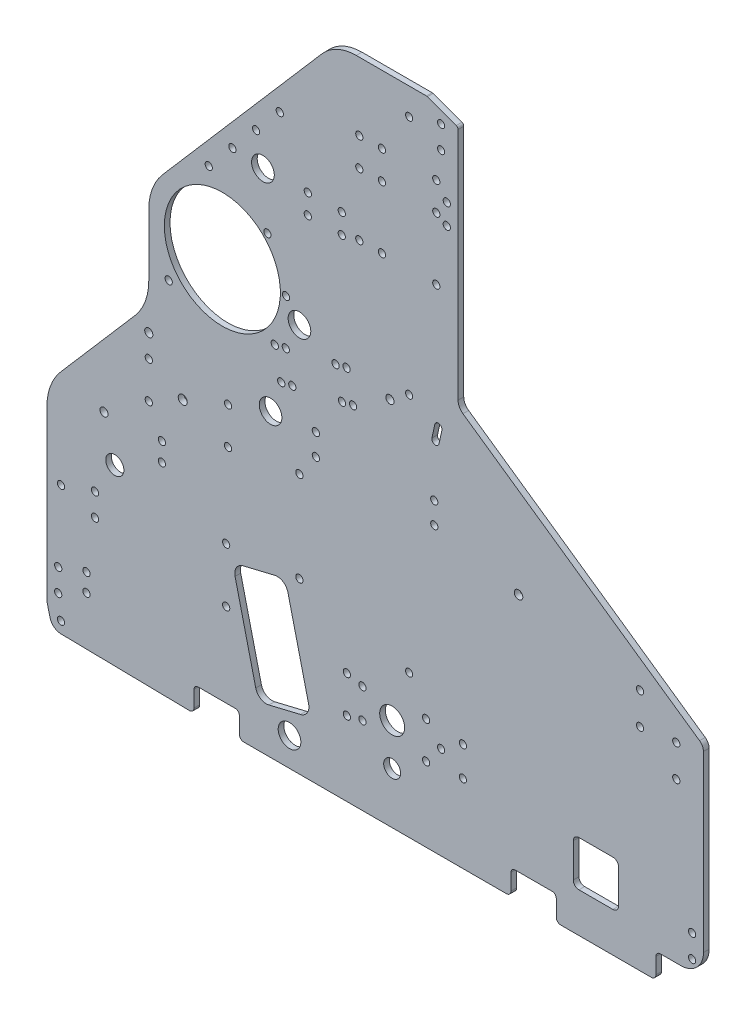
SolidWorks part; units mm, degrees
ref_plane "Front Plane" through (0, 0, 0) normal (0, 0, 1) x (1, 0, 0)
ref_plane "Top Plane" through (0, 0, 0) normal (0, 1, 0) x (1, 0, 0)
ref_plane "Right Plane" through (0, 0, 0) normal (1, 0, 0) x (0, 0, -1)
sketch "Sketch1" plane through (0, 0, 0) normal (0, 0, 1) x (1, 0, 0)
  line L0 (82.55, -20.32) -> (82.55, -6.35)
  line L2 (0, 0) -> (0, 157.48)
  line L4 (368.3, -20.32) -> (368.3, 106.68)
  line L5 (82.55, -6.35) -> (107.95, -6.35)
  line L6 (107.95, -6.35) -> (107.95, -20.32)
  line L7 (107.95, -20.32) -> (260.35, -20.32)
  line L8 (260.35, -20.32) -> (260.35, -6.35)
  line L9 (260.35, -6.35) -> (285.75, -6.35)
  line L10 (285.75, -6.35) -> (285.75, -20.32)
  line L11 (285.75, -20.32) -> (368.3, -20.32)
  line L12 (361.95, 12.7) -> (368.3, 12.7) construction
  line L13 (0, 0) -> (6.35, 0) construction
  line L14 (0.1896, -7.8901) -> (1.7771, -14.2401)
  line L15 (7.8295, -19.0491) -> (82.55, -20.32)
  line L16 (0, 0) -> (0, -6.35)
  line L17 (76.2, 128.905) -> (79.375, 128.905) construction
  line L18 (57.15, 118.5863) -> (101.6, 118.5862) construction
  line L19 (57.15, 118.5863) -> (57.15, 139.2238) construction
  line L20 (101.6, 118.5862) -> (101.6, 139.2237) construction
  line L21 (57.15, 139.2238) -> (101.6, 139.2237) construction
  line L22 (57.15, 118.5863) -> (101.6, 139.2237) construction
  line L23 (101.6, 118.5862) -> (57.15, 139.2238) construction
  line L24 (101.6, 139.2237) -> (125.4682, 147.9111) construction
  line L25 (203.2, 59.805) -> (203.2, 194.805) construction
  line L26 (203.2, 194.805) -> (203.2, 329.805) construction
  line L27 (355.6, 332.105) -> (330.2, 332.105) construction
  line L28 (330.2, 332.105) -> (330.2, 217.805) construction
  line L29 (330.2, 217.805) -> (355.6, 217.805) construction
  line L30 (355.6, 217.805) -> (355.6, 332.105) construction
  line L31 (203.2, 344.805) -> (203.2, 194.805) construction
  line L32 (50.8, 332.105) -> (76.2, 332.105) construction
  line L33 (76.2, 332.105) -> (76.2, 217.805) construction
  line L34 (50.8, 217.805) -> (50.8, 332.105) construction
  line L35 (76.2, 217.805) -> (50.8, 217.805) construction
  line L36 (213.2, 344.805) -> (230.6638, 338.455)
  line L37 (203.2, 344.805) -> (161.925, 344.805)
  line L38 (203.2, 344.805) -> (213.2, 344.805)
  line L39 (348.5362, 344.805) -> (413.4623, 344.805)
  line L40 (348.5362, 344.805) -> (230.6638, 344.805) construction
  line L42 (161.925, 344.805) -> (0, 157.48)
  line L44 (230.6638, 338.455) -> (230.6638, 202.565)
  line L45 (230.6638, 202.565) -> (368.3, 106.68)
  line L46 (213.2, 344.805) -> (-141.0713, 344.805) construction
  circle A0 centre (6.35, 0) radius 2.032
  circle A1 centre (6.35, 12.7) radius 2.032
  circle A2 centre (361.95, 0) radius 2.032
  circle A3 centre (361.95, 12.7) radius 2.032
  arc A5 (1.7771, -14.2401) -> (7.8295, -19.0491) centre (7.9375, -12.7) ccw
  circle A6 centre (7.9375, -12.7) radius 2.032
  arc A7 (0, -6.35) -> (0.1896, -7.8901) centre (6.35, -6.35) ccw
  circle A8 centre (38.1, 78.105) radius 5.08
  circle A9 centre (76.2, 128.905) radius 2.54
  circle A10 centre (101.6, 118.5862) radius 2.032
  circle A11 centre (101.6, 139.2237) radius 2.032
  circle A12 centre (57.15, 139.2238) radius 2.032
  circle A13 centre (57.15, 118.5863) radius 2.032
  circle A15 centre (203.2, 59.805) radius 2
  circle A16 centre (203.2, 194.805) radius 2
  circle A17 centre (203.2, 329.805) radius 2
  circle A18 centre (63.5, 313.055) radius 2.032
  circle A20 centre (355.6, 332.105) radius 2.032
  circle A21 centre (330.2, 332.105) radius 2.032
  circle A22 centre (355.6, 217.805) radius 2.032
  circle A23 centre (330.2, 217.805) radius 2.032
  circle A24 centre (50.8, 332.105) radius 2.032
  circle A25 centre (76.2, 332.105) radius 2.032
  circle A26 centre (50.8, 217.805) radius 2.032
  circle A27 centre (76.2, 217.805) radius 2.032
  circle A28 centre (221.1381, 335.28) radius 2
  circle A29 centre (224.3138, 298.831) radius 2.032
  circle A30 centre (353.06, 100.7351) radius 2.032
  circle A31 centre (332.74, 115.9751) radius 2.032
  circle A32 centre (332.74, 98.1951) radius 2.032
  circle A33 centre (353.06, 82.9551) radius 2.032
  circle A34 centre (117.3562, 280.4276) radius 2.032
  circle A35 centre (104.0678, 265.0548) radius 2.032
  circle A36 centre (90.7795, 249.682) radius 2.032
  circle A38 centre (130.6445, 295.8004) radius 2.032
  circle A39 centre (68.326, 182.9237) radius 2.032
  circle A40 centre (224.3138, 287.401) radius 2.032
  circle A41 centre (125.4682, 147.9111) radius 6.35
  circle A42 centre (221.1381, 322.58) radius 2
  point P82 (203.2, 344.805)
  point P90 (368.3, 62.484)
  dimension "D6" = 4.064
  dimension "D10" = 6.35
  dimension "D11" = 4.064
  dimension "D17" = 38.1
  dimension "D27" = 4
  dimension "D31" = 4.064
  dimension "D32" = 41.275
  dimension "D36" = 4.064
  dimension "D47" = 39.624
  dimension "D48" = 4.064
  dimension "D25" = 5.08
  dimension "D26" = 4.064
  dimension "D52" = 4.064
  dimension "D65" = 4.064
  dimension "D69" = 10.16
  dimension "D72" = 12.7
  dimension "D2" = 127
  dimension "D3" = 13.97
  dimension "D4" = 25.4
  dimension "D5" = 152.4
  dimension "D7" = 12.7
  dimension "D8" = 6.35
  dimension "D9" = 20.32
  dimension "D12" = 12.7
  dimension "D13" = 1.5875
  dimension "D14" = 82.55
  dimension "D15" = 368.3
  dimension "D16" = 6.35
  dimension "D18" = 98.425
  dimension "D19" = 38.1
  dimension "D20" = 50.8
  dimension "D21" = 3.175
  dimension "D22" = 270
  dimension "D23" = 20.6375
  dimension "D24" = 44.45
  dimension "D28" = 135
  dimension "D29" = 12.7
  dimension "D30" = 15
  dimension "D33" = 63.5
  dimension "D34" = 27.4638
  dimension "D35" = 12.7
  dimension "D37" = 114.3
  dimension "D38" = 25.4
  dimension "D39" = 12.7
  dimension "D40" = 157.48
  dimension "D41" = 142.24
  dimension "D42" = 365.125
  dimension "D43" = 10
  dimension "D44" = 6.35
  dimension "D45" = 31.75
  dimension "D46" = 3.175
  dimension "D49" = 6.35
  dimension "D50" = 203.2
  dimension "D51" = 15.24
  dimension "D53" = 17.78
  dimension "D54" = 17.78
  dimension "D55" = 20.32
  dimension "D56" = 15.24
  dimension "D57" = 92.202
  dimension "D58" = 8.382
  dimension "D59" = 20.32
  dimension "D60" = 20.32
  dimension "D61" = 8.382
  dimension "D62" = 20.32
  dimension "D63" = 8.382
  dimension "D64" = 8.382
  dimension "D66" = 35.052
  dimension "D67" = 68.326
  dimension "D68" = 11.43
  dimension "D70" = 25.4
  dimension "D71" = 110
  dimension "D73" = 17.9381
  dimension "D74" = 12.7
extrude "Boss-Extrude1" add sketch "Sketch1" along normal blind 3.175 contours L16 A7 L14 A5 L15 L2 A0 A1 A6 region at (171.5045, 119.4976, 0)
fillet "Fillet1" radius 2.286 4 edges at (285.75, -6.35, 1.5875) (107.95, -6.35, 1.5875) (260.35, -6.35, 1.5875) (82.55, -6.35, 1.5875)
fillet "Fillet2" radius 6.35 1 edges at (230.6638, 202.565, 1.5875)
sketch "Sketch2" plane through (0, 0, 0) normal (0, 0, -1) x (-1, 0, 0)
  circle A0 centre (-100.5528, 71.086) radius 2.032 construction
  circle A1 centre (-100.5528, 40.606) radius 2.032 construction
  circle A2 centre (-22.225, 18.2025) radius 2.032 construction
  circle A3 centre (-22.225, 8.0425) radius 2.032 construction
  circle A4 centre (-100.5528, 71.086) radius 2.032
  circle A5 centre (-100.5528, 40.606) radius 2.032
  circle A6 centre (-22.225, 18.2025) radius 2.032
  circle A7 centre (-22.225, 8.0425) radius 2.032
extrude "Cut-Extrude1" cut sketch "Sketch2" against normal through all
fillet "Fillet3" radius 1.5875 2 edges at (230.6638, 338.455, 1.5875) (213.2, 344.805, 1.5875)
sketch "Sketch3" plane through (0, 0, 3.175) normal (0, 0, 1) x (1, 0, 0)
  line L0 (132.9524, 63.2646) -> (132.7215, 64.2281) construction
  line L1 (128.3814, 66.8897) -> (110.6828, 62.6472) construction
  line L2 (114.5132, 58.4237) -> (126.8822, 61.3887) construction
  line L3 (108.0212, 58.3071) -> (108.2522, 57.3436) construction
  line L4 (131.2006, 57.703) -> (140.0164, 20.9265) construction
  line L5 (144.0993, 16.7636) -> (132.9524, 63.2646) construction
  line L6 (108.2522, 57.3436) -> (119.3991, 10.8426) construction
  line L7 (121.1509, 16.4042) -> (112.3351, 53.1807) construction
  line L8 (119.3991, 10.8426) -> (119.6301, 9.8791) construction
  line L9 (144.3303, 15.8001) -> (144.0993, 16.7636) construction
  line L10 (137.8383, 15.6835) -> (125.4694, 12.7185) construction
  line L11 (123.9701, 7.2175) -> (141.6687, 11.4601) construction
  line L12 (132.9524, 63.2646) -> (132.7215, 64.2281)
  line L13 (128.3814, 66.8897) -> (110.6828, 62.6472)
  line L14 (114.5132, 58.4237) -> (126.8822, 61.3887)
  line L15 (108.0212, 58.3071) -> (108.2522, 57.3436)
  line L16 (131.2006, 57.703) -> (140.0164, 20.9265)
  line L17 (144.0993, 16.7636) -> (132.9524, 63.2646)
  line L18 (108.2522, 57.3436) -> (119.3991, 10.8426)
  line L19 (121.1509, 16.4042) -> (112.3351, 53.1807)
  line L20 (119.3991, 10.8426) -> (119.6301, 9.8791)
  line L21 (144.3303, 15.8001) -> (144.0993, 16.7636)
  line L22 (137.8383, 15.6835) -> (125.4694, 12.7185)
  line L23 (123.9701, 7.2175) -> (141.6687, 11.4601)
  line L24 (127.7894, 69.3598) -> (110.0908, 65.1172)
  line L25 (105.5512, 57.715) -> (105.7822, 56.7515)
  line L26 (105.7822, 56.7515) -> (116.9291, 10.2505)
  line L27 (116.9291, 10.2505) -> (117.16, 9.287)
  line L28 (124.5622, 4.7475) -> (142.2608, 8.99)
  line L29 (146.8003, 16.3922) -> (146.5694, 17.3557)
  line L30 (146.5694, 17.3557) -> (135.4225, 63.8567)
  line L31 (135.4225, 63.8567) -> (135.1915, 64.8202)
  line L32 (14.605, -0.1369) -> (103.7278, 32.3011) construction
  line L33 (14.605, -0.1369) -> (103.7278, 32.3011)
  line L34 (0, -6.35) -> (0, 157.48) construction
  line L35 (-39.6666, 74.7152) -> (103.7278, 126.9065) construction
  line L36 (26.9875, 46.9531) -> (26.9875, 59.6531) construction
  line L37 (107.95, -20.32) -> (260.35, -20.32) construction
  line L38 (64.5259, 92.5258) -> (64.5259, 102.9405) construction
  line L39 (131.6538, 14.201) -> (136.0946, -4.3242) construction
  arc A0 (132.7215, 64.2281) -> (128.6308, 66.9403) centre (129.2206, 63.3889) ccw construction
  arc A1 (110.6828, 62.6472) -> (110.4377, 62.5791) centre (111.522, 59.1463) ccw construction
  arc A2 (128.6308, 66.9403) -> (128.3814, 66.8897) centre (129.2206, 63.3889) ccw construction
  arc A3 (110.4377, 62.5791) -> (108.0212, 58.3071) centre (111.522, 59.1463) ccw construction
  arc A4 (119.6301, 9.8791) -> (123.7207, 7.1669) centre (123.1309, 10.7183) ccw construction
  arc A5 (141.9139, 11.5281) -> (144.3303, 15.8001) centre (140.8295, 14.9609) ccw construction
  arc A6 (141.6687, 11.4601) -> (141.9139, 11.5281) centre (140.8295, 14.9609) ccw construction
  arc A7 (123.7207, 7.1669) -> (123.9701, 7.2175) centre (123.1309, 10.7183) ccw construction
  arc A8 (132.7215, 64.2281) -> (128.6308, 66.9403) centre (129.2206, 63.3889) ccw
  arc A9 (110.6828, 62.6472) -> (110.4377, 62.5791) centre (111.522, 59.1463) ccw
  arc A10 (128.6308, 66.9403) -> (128.3814, 66.8897) centre (129.2206, 63.3889) ccw
  arc A11 (110.4377, 62.5791) -> (108.0212, 58.3071) centre (111.522, 59.1463) ccw
  arc A12 (119.6301, 9.8791) -> (123.7207, 7.1669) centre (123.1309, 10.7183) ccw
  arc A13 (141.9139, 11.5281) -> (144.3303, 15.8001) centre (140.8295, 14.9609) ccw
  arc A14 (141.6687, 11.4601) -> (141.9139, 11.5281) centre (140.8295, 14.9609) ccw
  arc A15 (123.7207, 7.1669) -> (123.9701, 7.2175) centre (123.1309, 10.7183) ccw
  arc A16 (110.0908, 65.1172) -> (109.6726, 65.0012) centre (111.522, 59.1463) ccw
  arc A17 (109.6726, 65.0012) -> (105.5512, 57.715) centre (111.522, 59.1463) ccw
  arc A18 (117.16, 9.287) -> (124.1369, 4.6613) centre (123.1309, 10.7183) ccw
  arc A19 (124.1369, 4.6613) -> (124.5622, 4.7475) centre (123.1309, 10.7183) ccw
  arc A20 (142.2608, 8.99) -> (142.6789, 9.1061) centre (140.8295, 14.9609) ccw
  arc A21 (142.6789, 9.1061) -> (146.8003, 16.3922) centre (140.8295, 14.9609) ccw
  arc A22 (135.1915, 64.8202) -> (128.2147, 69.446) centre (129.2206, 63.3889) ccw
  arc A23 (128.2147, 69.446) -> (127.7894, 69.3598) centre (129.2206, 63.3889) ccw
  circle A24 centre (136.0946, -4.3242) radius 6.35
  circle A26 centre (134.1437, 208.2281) radius 2.032 construction
  circle A33 centre (26.9875, 46.9531) radius 2.032
  circle A34 centre (26.9875, 59.6531) radius 2.032
  circle A35 centre (7.9375, 53.3031) radius 2.032
  circle A37 centre (32.0306, 100.8109) radius 32.385 construction
  circle A38 centre (32.0306, 100.8109) radius 2.286
  circle A39 centre (123.682, 233.4851) radius 2.032 construction
  circle A40 centre (64.5259, 102.9405) radius 2.032
  circle A41 centre (64.5259, 92.5258) radius 2.032
  circle A42 centre (134.1437, 208.2281) radius 2.032
  circle A43 centre (123.682, 233.4851) radius 2.032
  ellipse E0 centre (124.5974, 48.8487) end of major axis (128.5376, 61.3578) minor radius 6 (131.2006, 57.703) -> (126.8822, 61.3887) ccw construction
  ellipse E1 centre (122.2349, 48.2824) end of major axis (113.0518, 57.6456) minor radius 6 (114.5132, 58.4237) -> (112.3351, 53.1807) ccw construction
  ellipse E2 centre (127.7541, 25.2585) end of major axis (131.6942, 37.7675) minor radius 6 (121.1509, 16.4042) -> (125.4694, 12.7185) ccw construction
  ellipse E3 centre (130.1166, 25.8248) end of major axis (139.2998, 16.4616) minor radius 6 (137.8383, 15.6835) -> (140.0164, 20.9265) ccw construction
  ellipse E4 centre (124.5974, 48.8487) end of major axis (120.6573, 36.3397) minor radius 6 (131.2006, 57.703) -> (126.8822, 61.3887) ccw
  ellipse E5 centre (122.2349, 48.2824) end of major axis (131.4181, 38.9192) minor radius 6 (114.5132, 58.4237) -> (112.3351, 53.1807) ccw
  ellipse E6 centre (127.7541, 25.2585) end of major axis (131.6942, 37.7675) minor radius 6 (121.1509, 16.4042) -> (125.4694, 12.7185) ccw
  ellipse E7 centre (130.1166, 25.8248) end of major axis (139.2998, 16.4616) minor radius 6 (137.8383, 15.6835) -> (140.0164, 20.9265) ccw
  point P93 (26.9875, 53.3031)
  point P115 (32.0306, 100.8109)
  dimension "D3" = 64.77
  dimension "D4" = 4.572
  dimension "D8" = 4.064
  dimension "D13" = 12.7
  dimension "D2" = 88.9
  dimension "D5" = 7.9375
  dimension "D6" = 19.05
  dimension "D7" = 73.6231
  dimension "D9" = 12.7
  dimension "D10" = 10.4147
  dimension "D11" = 37.5384
  dimension "D12" = 45.5727
  dimension "D14" = 19.05
  dimension "D1" = 2.54
extrude "Cut-Extrude2" cut sketch "Sketch3" against normal through all contours A22 A23 L24 A16 A17 L25 L26 L27 A18 A19 L28 A20 A21 L29 L30 L31 A15 A12 L20 L18 L15 A11 A9 L13 A10 A8 L12 L17 L21 A13 A14 L23 | A12 A15 L23 A14 A13 L21 L17 L12 A8 A10 L13 A9 A11 L15 L18 L20 E7 L22 E6 L19 E5 L14 E4 L16 | L22 E7 L16 E4 L14 E5 L19 E6 | A38 | A41 | A40 | A35 | A34 | A33 | A43 | A42 | A24 region at (137.844, 39.8506, 3.175) region at (126.1758, 37.0536, 3.175) region at (128.1544, 68.6507, 3.175) region at (32.0306, 100.8109, 3.175) region at (64.5259, 102.9405, 3.175) region at (64.5259, 92.5258, 3.175)
sketch "Sketch4" plane through (0, 0, 3.175) normal (0, 0, 1) x (1, 0, 0)
  line L0 (57.15, 139.2238) -> (101.6, 139.2237) construction
  line L1 (168.275, 21.4312) -> (212.725, 21.4312) construction
  line L2 (168.275, 21.4312) -> (168.275, 42.0687) construction
  line L3 (168.275, 42.0687) -> (212.725, 42.0687) construction
  line L4 (212.725, 21.4312) -> (212.725, 42.0687) construction
  line L5 (168.275, 21.4312) -> (212.725, 42.0687) construction
  line L6 (168.275, 42.0687) -> (212.725, 21.4312) construction
  line L7 (57.15, 118.5863) -> (57.15, 139.2238) construction
  line L8 (107.95, -20.32) -> (260.35, -20.32) construction
  line L9 (193.675, 31.75) -> (177.005, 31.75) construction
  line L10 (190.5, 31.75) -> (193.675, 31.75) construction
  line L11 (6.35, 12.7) -> (361.95, 12.7) construction
  line L12 (107.95, -6.35) -> (107.95, -20.32) construction
  line L13 (193.675, 31.75) -> (220.6625, 31.75) construction
  line L14 (177.005, 23.4569) -> (177.005, 40.0431) construction
  line L15 (213.2, 44.805) -> (193.2, 44.805) construction
  line L16 (213.2, 44.805) -> (213.2, 344.805) construction
  line L17 (213.2, 344.805) -> (193.2, 344.805) construction
  line L18 (193.2, 44.805) -> (193.2, 344.805) construction
  line L19 (213.2, 44.805) -> (193.2, 344.805) construction
  line L20 (213.2, 344.805) -> (193.2, 44.805) construction
  line L21 (226.1381, 335.28) -> (226.1381, 31.75) construction
  line L22 (237.33, 40.0431) -> (233.3612, 40.0431) construction
  line L23 (237.33, 23.4569) -> (233.3612, 23.4569) construction
  circle A0 centre (168.275, 42.0687) radius 2.032
  circle A1 centre (212.725, 42.0687) radius 2.032
  circle A2 centre (212.725, 21.4312) radius 2.032
  circle A3 centre (168.275, 21.4312) radius 2.032
  circle A4 centre (193.675, 31.75) radius 6.985
  circle A7 centre (220.6625, 31.75) radius 14.2875 construction
  circle A8 centre (193.675, 31.75) radius 12.7 construction
  circle A9 centre (177.005, 40.0431) radius 2.032
  circle A10 centre (177.005, 23.4569) radius 2.032
  circle A11 centre (237.33, 40.0431) radius 2.032 construction
  circle A12 centre (237.33, 23.4569) radius 2.032 construction
  circle A13 centre (193.675, 8.4667) radius 4.7625
  circle A14 centre (221.1381, 31.75) radius 2.032
  circle A15 centre (221.1381, 31.75) radius 5 construction
  circle A16 centre (221.1381, 335.28) radius 5 construction
  circle A17 centre (233.3612, 23.4569) radius 2.032
  circle A18 centre (233.3612, 40.0431) radius 2.032
  point P0 (190.5, 31.75)
  point P26 (203.2, 194.805)
  point P38 (177.005, 31.75)
  dimension "D1" = 4.064
  dimension "D4" = 13.97
  dimension "D7" = 9.525
  dimension "D10" = 25.4
  dimension "D11" = 28.575
  dimension "D16" = 10
  dimension "D17" = 4.064
  dimension "D18" = 10
  dimension "D2" = 52.07
  dimension "D3" = 3.175
  dimension "D5" = 82.55
  dimension "D6" = 26.9875
  dimension "D8" = 20
  dimension "D9" = 300
  dimension "D12" = 16.67
  dimension "D13" = 16.5862
  dimension "D14" = 60.325
  dimension "D15" = 23.2833
  dimension "D19" = 3.9688
extrude "Cut-Extrude3" cut sketch "Sketch4" against normal through all
sketch "Sketch5" plane through (0, 0, 0) normal (0, 0, -1) x (-1, 0, 0)
  line L0 (-57.15, 223.5947) -> (-57.15, 165.3337)
  line L1 (-161.925, 344.805) -> (-52.7201, 218.4699) construction
  line L2 (-57.15, 165.3337) -> (0, 99.219)
  line L3 (0, -6.35) -> (0, 157.48) construction
  line L4 (-147.864, -30.311) -> (-147.864, -16.0874)
  line L5 (-50.4199, 215.8089) -> (0, 157.48) construction
  line L6 (-57.15, 223.5947) -> (0, 157.48)
  line L7 (0, 157.48) -> (0, 99.219)
  line L8 (-98.425, 208.2281) -> (-141.6756, 197.9719) construction
  line L10 (-341.63, -6.35) -> (-341.63, -21.2964)
  line L12 (-371.0782, -6.35) -> (-341.63, -6.35)
  line L13 (-285.75, -20.32) -> (-368.3, -20.32) construction
  line L14 (-371.0782, -6.35) -> (-371.0782, -21.2964)
  line L15 (-371.0782, -21.2964) -> (-341.63, -21.2964)
  circle A0 centre (-98.425, 208.2281) radius 32.5437
  circle A1 centre (-141.6756, 197.9719) radius 6.35
  circle A3 centre (-264.5736, 128.3328) radius 2.39
  dimension "D3" = 65.0875
  dimension "D7" = 12.7
  dimension "D8" = 4.78
  dimension "D1" = 38.1
  dimension "D2" = 57.15
  dimension "D4" = 41.275
  dimension "D5" = 41.275
  dimension "D6" = 13.97
  dimension "D9" = 22.2382
  dimension "D10" = 117.7733
  dimension "D11" = 11.6447
  dimension "D12" = 123.5853
  dimension "D14" = 62.5
  dimension "D13" = 44.45
extrude "Cut-Extrude5" cut sketch "Sketch5" against normal through all contours A0 | L7 L6 L0 L2 | A3 | L14 L15 L10 L12 | A1 region at (28.575, 161.4068, 0) region at (356.3541, -13.8232, 0) region at (98.425, 208.2281, 0) region at (264.5736, 128.3328, 0)
fillet "Fillet4" radius 31.75 3 edges at (0, 99.219, 1.5875) (57.15, 165.3337, 1.5875) (57.15, 223.5947, 1.5875)
sketch "Sketch6" plane through (0, 0, 3.175) normal (0, 0, 1) x (1, 0, 0)
  line L0 (285.75, -20.32) -> (341.63, -20.32) construction
  line L1 (298.45, 27.305) -> (317.5, 27.305)
  line L2 (295.275, 24.13) -> (295.275, 5.08)
  line L3 (298.45, 1.905) -> (317.5, 1.905)
  line L4 (320.675, 24.13) -> (320.675, 5.08)
  line L5 (295.275, 27.305) -> (320.675, 1.905) construction
  line L6 (295.275, 1.905) -> (320.675, 27.305) construction
  line L7 (368.3, -6.35) -> (368.3, 106.68) construction
  arc A0 (295.275, 5.08) -> (298.45, 1.905) centre (298.45, 5.08) ccw
  arc A1 (317.5, 1.905) -> (320.675, 5.08) centre (317.5, 5.08) ccw
  arc A2 (317.5, 27.305) -> (320.675, 24.13) centre (317.5, 24.13) cw
  arc A3 (298.45, 27.305) -> (295.275, 24.13) centre (298.45, 24.13) ccw
  point P0 (307.975, 14.605)
  dimension "D2" = 3.175
  dimension "D1" = 25.4
  dimension "D3" = 22.225
  dimension "D4" = 47.625
extrude "Cut-Extrude6" cut sketch "Sketch6" against normal through all
fillet "Fillet5" radius 25.4 1 edges at (161.925, 344.805, 1.5875)
sketch "Sketch8" plane through (0, 0, 0) normal (0, 0, -1) x (-1, 0, 0)
  line L0 (-230.6638, 337.343) -> (-230.6638, 205.8802) construction
  line L1 (-230.6638, 255.905) -> (-175.26, 255.905) construction
  line L2 (-175.26, 255.905) -> (-175.26, 306.705) construction
  line L3 (-175.26, 306.705) -> (-230.6638, 306.705) construction
  line L4 (-173.5432, 344.805) -> (-212.9203, 344.805) construction
  line L7 (-107.95, -20.32) -> (-260.35, -20.32) construction
  circle A0 centre (-218.44, 290.83) radius 3.9687
  circle A1 centre (-218.44, 290.83) radius 2.032
  circle A2 centre (218.44, 265.7972) radius 3.9687
  circle A3 centre (218.44, 265.7972) radius 2.032
  circle A4 centre (-205.74, 290.83) radius 3.9687
  circle A5 centre (-205.74, 290.83) radius 2.032
  circle A6 centre (-187.96, 290.83) radius 3.9687
  circle A7 centre (-187.96, 290.83) radius 2.032
  circle A8 centre (-187.96, 306.705) radius 2.032
  circle A9 centre (-175.26, 290.83) radius 3.9687
  circle A10 centre (-175.26, 290.83) radius 2.032
  circle A11 centre (-205.74, 306.705) radius 2.032
  circle A13 centre (-205.74, 255.905) radius 2.032
  circle A14 centre (-187.96, 255.905) radius 2.032
  circle A16 centre (-218.44, 306.705) radius 2.032
  circle A17 centre (-175.26, 306.705) radius 2.032
  circle A18 centre (-175.26, 255.905) radius 2.032
  circle A19 centre (-218.44, 255.905) radius 2.032
  circle A20 centre (-218.44, 306.705) radius 3.9687
  circle A21 centre (-205.74, 306.705) radius 3.9687
  circle A22 centre (-175.26, 306.705) radius 3.9687
  circle A23 centre (-218.44, 255.905) radius 3.9687
  circle A24 centre (-205.74, 255.905) radius 3.9687
  circle A25 centre (-187.96, 255.905) radius 3.9687
  circle A26 centre (-175.26, 255.905) radius 3.9687
  circle A27 centre (-187.96, 306.705) radius 3.9687
  dimension "D1" = 7.9375
  dimension "D7" = 4.064
  dimension "D13" = 12.2237
  dimension "D2" = 12.2237
  dimension "D3" = 12.7
  dimension "D4" = 17.78
  dimension "D5" = 12.7
  dimension "D6" = 88.9
  dimension "D8" = 38.1
  dimension "D9" = 17.78
  dimension "D10" = 12.7
  dimension "D11" = 55.4037
  dimension "D12" = 12.7
  dimension "D14" = 311.15
extrude "Cut-Extrude7" cut sketch "Sketch8" against normal through all contours A16 | A17 | A18 | A19 | A8 | A14 | A1 | A7 | A10 region at (218.44, 306.705, 0) region at (175.26, 306.705, 0) region at (175.26, 255.905, 0) region at (218.44, 255.905, 0)
sketch "Sketch10" plane through (0, 0, 3.175) normal (0, 0, 1) x (1, 0, 0)
  circle A4 centre (141.6425, 74.6844) radius 2.032 construction
  circle A5 centre (141.6425, 125.4844) radius 2.032 construction
  circle A6 centre (141.6425, 74.6844) radius 2.032
  circle A7 centre (141.6425, 125.4844) radius 2.032
extrude "Cut-Extrude8" cut sketch "Sketch10" against normal through all
sketch "Sketch11" plane through (0, 0, 3.175) normal (0, 0, 1) x (1, 0, 0)
  ellipse E4 centre (150.8814, 138.43) end of major axis (150.8814, 140.462) minor radius 2.032
  ellipse E5 centre (150.8814, 150.495) end of major axis (150.8814, 152.527) minor radius 2.032
  ellipse E6 centre (217.3024, 150.495) end of major axis (217.3024, 152.527) minor radius 2.032
  ellipse E7 centre (217.3024, 138.43) end of major axis (217.3024, 140.462) minor radius 2.032
extrude "Cut-Extrude9" cut sketch "Sketch11" against normal through all
sketch "Sketch12" plane through (0, 0, 0) normal (0, 0, -1) x (-1, 0, 0)
  line L0 (-173.5432, 344.805) -> (-212.9203, 344.805) construction
  circle A0 centre (-165.4175, 264.635) radius 2.032
  circle A1 centre (-203.2, 329.805) radius 2 construction
  circle A2 centre (-165.4175, 253.5225) radius 2.032
  circle A3 centre (-146.3675, 253.5225) radius 2.032
  circle A4 centre (-146.3675, 264.635) radius 2.032
  dimension "D1" = 80.17
  dimension "D2" = 4.064
  dimension "D3" = 37.7825
  dimension "D4" = 11.1125
  dimension "D5" = 19.05
extrude "Cut-Extrude10" cut sketch "Sketch12" against normal through all
sketch "Sketch14" plane through (0, 0, 0) normal (0, 0, -1) x (-1, 0, 0)
  line L0 (-130.6445, 295.8004) -> (-121.1847, 263.6885) construction
  line L1 (-121.1847, 263.6885) -> (-90.7795, 249.682) construction
  line L2 (-154.3272, 336.0154) -> (-64.88, 232.5373) construction
  line L4 (-118.517, 269.4796) -> (-115.3937, 261.0208) construction
  line L5 (-118.517, 269.4796) -> (-126.9758, 266.3562) construction
  line L6 (-126.9758, 266.3562) -> (-123.8524, 257.8974) construction
  line L7 (-115.3937, 261.0208) -> (-123.8524, 257.8974) construction
  line L8 (-118.517, 269.4796) -> (-123.8524, 257.8974) construction
  line L9 (-126.9758, 266.3562) -> (-115.3937, 261.0208) construction
  circle A0 centre (-121.1847, 263.6885) radius 6.376
  dimension "D1" = 22.225
  dimension "D2" = 9.017
extrude "Cut-Extrude11" cut sketch "Sketch14" against normal through all
sketch "Sketch15" plane through (0, 0, 3.175) normal (0, 0, 1) x (1, 0, 0)
  line L1 (27.1508, 77.7471) -> (81.7263, 77.7471) construction
  line L2 (57.15, 139.2238) -> (57.15, 151.9238) construction
  line L3 (27.1508, 77.7471) -> (52.3291, 153.5255) construction
  line L4 (56.0505, 156.8833) -> (192.439, 187.1199) construction
  circle A0 centre (27.1508, 77.7471) radius 2.159 construction
  circle A1 centre (27.1508, 77.7471) radius 2.159 construction
  circle A2 centre (57.15, 139.2238) radius 2.032 construction
  circle A3 centre (57.15, 139.2238) radius 2.032 construction
  circle A4 centre (57.15, 151.9238) radius 2.286
  circle A5 centre (192.439, 187.1199) radius 2.286
  circle A6 centre (57.15, 151.9238) radius 5.08 construction
  arc A9 (163.8737, 173.6806) -> (164.5125, 170.7993) centre (165.557, 172.5423) ccw construction
  arc A10 (173.4398, 172.7784) -> (172.801, 175.6597) centre (171.7565, 173.9167) ccw construction
  arc A11 (172.801, 175.6597) -> (173.4398, 172.7784) centre (171.7565, 173.9167) ccw construction
  arc A12 (164.5125, 170.7993) -> (163.8737, 173.6806) centre (165.557, 172.5423) ccw construction
  arc A13 (169.1589, 192.0883) -> (169.7976, 189.2071) centre (168.1143, 190.3453) ccw construction
  arc A14 (169.7976, 189.2071) -> (169.1589, 192.0883) centre (168.1143, 190.3453) ccw construction
  arc A15 (160.2316, 190.1092) -> (160.8704, 187.2279) centre (161.9149, 188.9709) ccw construction
  arc A16 (160.8704, 187.2279) -> (160.2316, 190.1092) centre (161.9149, 188.9709) ccw construction
  arc A17 (129.7766, 166.1214) -> (130.4154, 163.2402) centre (131.4599, 164.9832) ccw construction
  arc A18 (139.3426, 165.2193) -> (138.7039, 168.1005) centre (137.6593, 166.3576) ccw construction
  arc A19 (138.7039, 168.1005) -> (139.3426, 165.2193) centre (137.6593, 166.3576) ccw construction
  arc A20 (130.4154, 163.2402) -> (129.7766, 166.1214) centre (131.4599, 164.9832) ccw construction
  arc A21 (135.7005, 181.6479) -> (135.0617, 184.5292) centre (134.0172, 182.7862) ccw construction
  arc A22 (135.0617, 184.5292) -> (135.7005, 181.6479) centre (134.0172, 182.7862) ccw construction
  arc A23 (126.1345, 182.55) -> (126.7732, 179.6688) centre (127.8177, 181.4118) ccw construction
  arc A24 (126.7732, 179.6688) -> (126.1345, 182.55) centre (127.8177, 181.4118) ccw construction
  arc A25 (163.8737, 173.6806) -> (164.5125, 170.7993) centre (165.557, 172.5423) ccw
  arc A26 (173.4398, 172.7784) -> (172.801, 175.6597) centre (171.7565, 173.9167) ccw
  arc A27 (172.801, 175.6597) -> (173.4398, 172.7784) centre (171.7565, 173.9167) ccw
  arc A28 (164.5125, 170.7993) -> (163.8737, 173.6806) centre (165.557, 172.5423) ccw
  arc A29 (169.1589, 192.0883) -> (169.7976, 189.2071) centre (168.1143, 190.3453) ccw
  arc A30 (169.7976, 189.2071) -> (169.1589, 192.0883) centre (168.1143, 190.3453) ccw
  arc A31 (160.2316, 190.1092) -> (160.8704, 187.2279) centre (161.9149, 188.9709) ccw
  arc A32 (160.8704, 187.2279) -> (160.2316, 190.1092) centre (161.9149, 188.9709) ccw
  arc A33 (129.7766, 166.1214) -> (130.4154, 163.2402) centre (131.4599, 164.9832) ccw
  arc A34 (139.3426, 165.2193) -> (138.7039, 168.1005) centre (137.6593, 166.3576) ccw
  arc A35 (138.7039, 168.1005) -> (139.3426, 165.2193) centre (137.6593, 166.3576) ccw
  arc A36 (130.4154, 163.2402) -> (129.7766, 166.1214) centre (131.4599, 164.9832) ccw
  arc A37 (135.7005, 181.6479) -> (135.0617, 184.5292) centre (134.0172, 182.7862) ccw
  arc A38 (135.0617, 184.5292) -> (135.7005, 181.6479) centre (134.0172, 182.7862) ccw
  arc A39 (126.1345, 182.55) -> (126.7732, 179.6688) centre (127.8177, 181.4118) ccw
  arc A40 (126.7732, 179.6688) -> (126.1345, 182.55) centre (127.8177, 181.4118) ccw
  dimension "D2" = 4.572
  dimension "D6" = 10.16
  dimension "D1" = 12.7
  dimension "D3" = 139.7
  dimension "D4" = 12.5
extrude "Cut-Extrude12" cut sketch "Sketch15" against normal through all
sketch "Sketch16" plane through (0, 0, 3.175) normal (0, 0, 1) x (1, 0, 0)
  circle A0 centre (98.425, 208.2281) radius 34.925 construction
  circle A1 centre (98.425, 208.2281) radius 34.925
  circle A2 centre (98.425, 208.2281) radius 36.195
  dimension "D1" = 1.27
fillet "Fillet6" radius 12.7 1 edges at (368.3, -6.35, 1.5875)
fillet "Fillet7" radius 5.08 1 edges at (368.3, 106.68, 1.5875)
fillet "Fillet8" radius 2.54 6 edges at (82.55, -20.32, 1.5875) (107.95, -20.32, 1.5875) (260.35, -20.32, 1.5875) (285.75, -20.32, 1.5875) (341.63, -20.32, 1.5875) (341.63, -6.35, 1.5875)
sketch "Sketch17" plane through (0, 0, 3.175) normal (0, 0, 1) x (1, 0, 0)
  line L0 (230.6638, 337.343) -> (230.6638, 205.8802) construction
  line L1 (173.5432, 344.805) -> (212.9203, 344.805) construction
  line L2 (217.9638, 179.705) -> (219.5961, 187.1481) construction
  line L3 (215.9789, 180.1403) -> (217.6113, 187.5834)
  line L4 (219.9486, 179.2697) -> (221.581, 186.7128)
  circle A0 centre (217.9638, 179.705) radius 2.032
  arc A1 (215.9789, 180.1403) -> (219.9486, 179.2697) centre (217.9638, 179.705) ccw
  arc A2 (221.581, 186.7128) -> (217.6113, 187.5834) centre (219.5961, 187.1481) ccw
  point P7 (218.7799, 183.4265)
  point P12 (216.3095, 180.885)
  point P13 (226.6429, 195.1918)
  dimension "D1" = 12.7
  dimension "D3" = 4.064
  dimension "D2" = 165.1
  dimension "D4" = 167.63
  dimension "D5" = 7.62
extrude "Cut-Extrude13" cut sketch "Sketch17" against normal through all contours L4 A2 L3 A1
